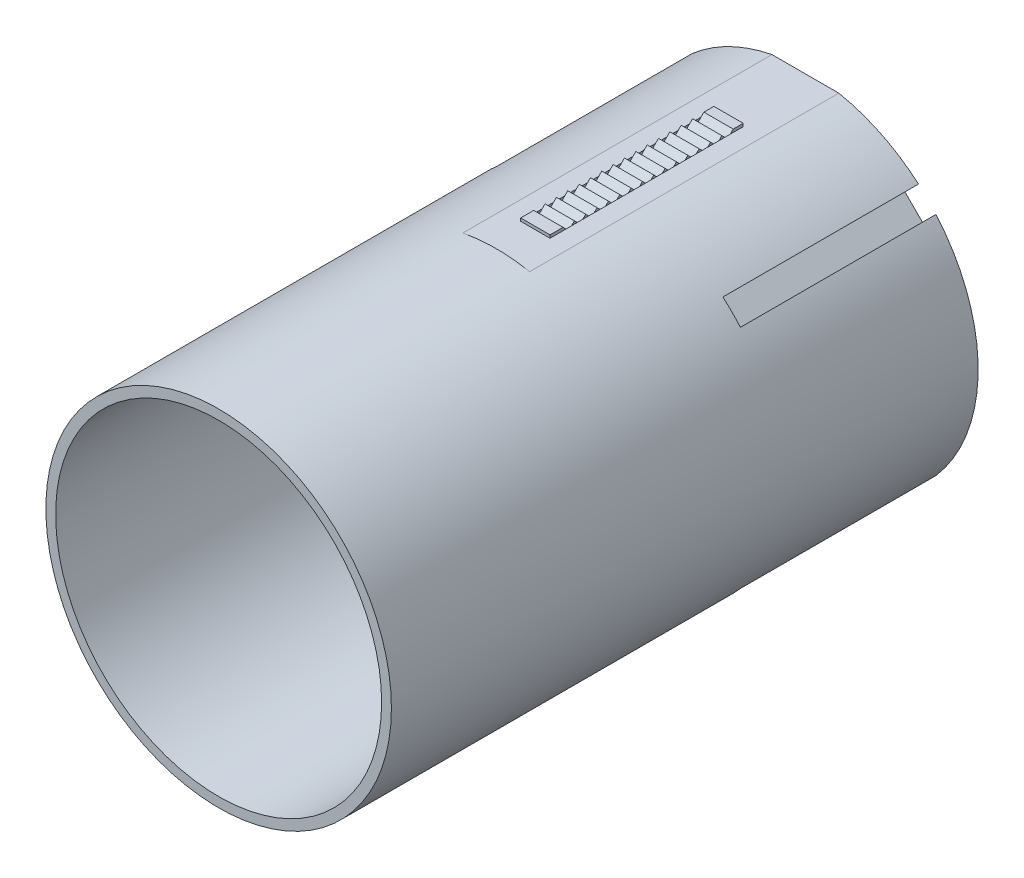
SolidWorks part; units mm, degrees
ref_plane "Ebene vorne" through (0, 0, 0) normal (0, 0, 1) x (1, 0, 0)
ref_plane "Ebene oben" through (0, 0, 0) normal (0, 1, 0) x (1, 0, 0)
ref_plane "Ebene rechts" through (0, 0, 0) normal (1, 0, 0) x (0, 0, -1)
sketch "Skizze1" plane through (0, 0, 0) normal (0, 0, 1) x (1, 0, 0)
  circle A0 centre (0, 0) radius 25
  circle A1 centre (0, 0) radius 26.5
  dimension "D1" = 50
  dimension "D2" = 1.5
extrude "Aufsatz-Linear austragen1" add sketch "Skizze1" along normal blind 90
sketch "Skizze2" plane through (0, 0, 0) normal (1, 0, 0) x (0, 0, -1)
  line L0 (0, 26.5) -> (0, 26)
  line L1 (0, -26.5) -> (0, 26.5) construction
  line L2 (0, 26) -> (-47.4208, 26)
  line L3 (-47.4208, 26) -> (-47.4208, 26.5)
  line L4 (0, 26.5) -> (-90, 26.5) construction
  line L5 (-47.4208, 26.5) -> (0, 26.5)
  dimension "D1" = 0.5
extrude "Schnitt-Linear austragen1" cut sketch "Skizze2" against normal through all and the other way through all
sketch "Skizze4" plane through (0, 0, 0) normal (0, 0, -1) x (-1, 0, 0)
  line L0 (0, 26) -> (0, 19.8792) construction
  line L1 (5.1235, 26) -> (-5.1235, 26) construction
  line L2 (8.5294, 23.5) -> (-8.5294, 23.5)
  line L4 (-8.5294, 23.5) -> (-5.3603, 25.2043)
  line L5 (-5.3603, 25.2043) -> (5.3603, 25.2043)
  line L6 (8.5294, 23.5) -> (5.3603, 25.2043)
  circle A0 centre (0, 0) radius 25 construction
  point P12 (0, 25.2043)
  point P13 (0, 23.5)
  dimension "D1" = 2.5
extrude "Aufsatz-Linear austragen2" add sketch "Skizze4" against normal up to surface (47.4208 mm away) up to face at (0, 26.25, 47.4208)
sketch "Skizze5" plane through (0, 0, 0) normal (1, 0, 0) x (0, 0, -1)
  line L0 (-41.4208, 26) -> (-41.4208, 25.9992)
  line L1 (0, 26) -> (-47.4208, 26) construction
  line L2 (-41.4208, 25.9992) -> (-11.7833, 25.9992) construction
  line L3 (-11.7833, 26) -> (-11.7833, 25.9992)
  line L4 (-11.7833, 25.9992) -> (-11.7833, 26.4492)
  line L5 (-41.4208, 25.9992) -> (-41.4208, 26.4492)
  line L6 (-41.4208, 26.4492) -> (-39.4208, 26.4492)
  line L7 (-11.7833, 26) -> (-41.4208, 26)
  line L8 (-39.4208, 26.4492) -> (-38.5508, 25.5792)
  line L9 (-38.5508, 25.5792) -> (-37.6808, 26.4492)
  line L10 (-39.4208, 26.4492) -> (-39.4208, 26) construction
  line L11 (-47.4208, 26) -> (-47.4208, 26.5) construction
  line L12 (-37.6808, 26.4492) -> (-36.8108, 25.5792)
  line L13 (-36.8108, 25.5792) -> (-35.9408, 26.4492)
  line L14 (-35.9408, 26.4492) -> (-35.0708, 25.5792)
  line L15 (-35.0708, 25.5792) -> (-34.2008, 26.4492)
  line L16 (-34.2008, 26.4492) -> (-33.3308, 25.5792)
  line L17 (-33.3308, 25.5792) -> (-32.4608, 26.4492)
  line L18 (-32.4608, 26.4492) -> (-31.5908, 25.5792)
  line L19 (-31.5908, 25.5792) -> (-30.7208, 26.4492)
  line L20 (-30.7208, 26.4492) -> (-29.8508, 25.5792)
  line L21 (-29.8508, 25.5792) -> (-28.9808, 26.4492)
  line L22 (-28.9808, 26.4492) -> (-28.1108, 25.5792)
  line L23 (-28.1108, 25.5792) -> (-27.2408, 26.4492)
  line L24 (-27.2408, 26.4492) -> (-26.3708, 25.5792)
  line L25 (-26.3708, 25.5792) -> (-25.5008, 26.4492)
  line L26 (-25.5008, 26.4492) -> (-24.6308, 25.5792)
  line L27 (-24.6308, 25.5792) -> (-23.7608, 26.4492)
  line L28 (-23.7608, 26.4492) -> (-22.8908, 25.5792)
  line L29 (-22.8908, 25.5792) -> (-22.0208, 26.4492)
  line L30 (-22.0208, 26.4492) -> (-21.1508, 25.5792)
  line L31 (-21.1508, 25.5792) -> (-20.2808, 26.4492)
  line L32 (-11.7833, 26.4492) -> (-13.3208, 26.4492)
  line L33 (-20.2808, 26.4492) -> (-19.4108, 25.5792)
  line L34 (-19.4108, 25.5792) -> (-18.5408, 26.4492)
  line L35 (-18.5408, 26.4492) -> (-17.6708, 25.5792)
  line L36 (-17.6708, 25.5792) -> (-16.8008, 26.4492)
  line L37 (-16.8008, 26.4492) -> (-15.9308, 25.5792)
  line L38 (-15.9308, 25.5792) -> (-15.0608, 26.4492)
  line L39 (-15.0608, 26.4492) -> (-14.1908, 25.5792)
  line L40 (-14.1908, 25.5792) -> (-13.3208, 26.4492)
  line L91 (29.3092, 25.5792) -> (30.1792, 26.4492) [skipped]
  line L92 (28.4392, 26.4492) -> (29.3092, 25.5792) [skipped]
  line L93 (27.5692, 25.5792) -> (28.4392, 26.4492) [skipped]
  line L94 (26.6992, 26.4492) -> (27.5692, 25.5792) [skipped]
  line L95 (25.8292, 25.5792) -> (26.6992, 26.4492) [skipped]
  line L96 (24.9592, 26.4492) -> (25.8292, 25.5792) [skipped]
  line L97 (24.0892, 25.5792) -> (24.9592, 26.4492) [skipped]
  line L98 (23.2192, 26.4492) -> (24.0892, 25.5792) [skipped]
  line L99 (22.3492, 25.5792) -> (23.2192, 26.4492) [skipped]
  line L100 (21.4792, 26.4492) -> (22.3492, 25.5792) [skipped]
  line L101 (20.6092, 25.5792) -> (21.4792, 26.4492) [skipped]
  line L102 (19.7392, 26.4492) -> (20.6092, 25.5792) [skipped]
  line L103 (18.8692, 25.5792) -> (19.7392, 26.4492) [skipped]
  line L104 (17.9992, 26.4492) -> (18.8692, 25.5792) [skipped]
  line L105 (17.1292, 25.5792) -> (17.9992, 26.4492) [skipped]
  line L106 (16.2592, 26.4492) -> (17.1292, 25.5792) [skipped]
  line L107 (15.3892, 25.5792) -> (16.2592, 26.4492) [skipped]
  line L108 (14.5192, 26.4492) -> (15.3892, 25.5792) [skipped]
  line L109 (13.6492, 25.5792) -> (14.5192, 26.4492) [skipped]
  line L110 (12.7792, 26.4492) -> (13.6492, 25.5792) [skipped]
  line L111 (11.9092, 25.5792) -> (12.7792, 26.4492) [skipped]
  line L112 (11.0392, 26.4492) -> (11.9092, 25.5792) [skipped]
  line L113 (10.1692, 25.5792) -> (11.0392, 26.4492) [skipped]
  line L114 (9.2992, 26.4492) -> (10.1692, 25.5792) [skipped]
  line L115 (8.4292, 25.5792) -> (9.2992, 26.4492) [skipped]
  line L116 (7.5592, 26.4492) -> (8.4292, 25.5792) [skipped]
  line L117 (6.6892, 25.5792) -> (7.5592, 26.4492) [skipped]
  line L118 (5.8192, 26.4492) -> (6.6892, 25.5792) [skipped]
  line L119 (4.9492, 25.5792) -> (5.8192, 26.4492) [skipped]
  line L120 (4.0792, 26.4492) -> (4.9492, 25.5792) [skipped]
  line L121 (3.2092, 25.5792) -> (4.0792, 26.4492) [skipped]
  line L122 (2.3392, 26.4492) -> (3.2092, 25.5792) [skipped]
  line L123 (1.4692, 25.5792) -> (2.3392, 26.4492) [skipped]
  line L124 (0.5992, 26.4492) -> (1.4692, 25.5792) [skipped]
  line L125 (-0.2708, 25.5792) -> (0.5992, 26.4492) [skipped]
  line L126 (-1.1408, 26.4492) -> (-0.2708, 25.5792) [skipped]
  line L127 (-2.0108, 25.5792) -> (-1.1408, 26.4492) [skipped]
  line L128 (-2.8808, 26.4492) -> (-2.0108, 25.5792) [skipped]
  line L129 (-3.7508, 25.5792) -> (-2.8808, 26.4492) [skipped]
  line L130 (-4.6208, 26.4492) -> (-3.7508, 25.5792) [skipped]
  line L131 (-5.4908, 25.5792) -> (-4.6208, 26.4492) [skipped]
  line L132 (-6.3608, 26.4492) -> (-5.4908, 25.5792) [skipped]
  line L133 (-7.2308, 25.5792) -> (-6.3608, 26.4492) [skipped]
  line L134 (-8.1008, 26.4492) -> (-7.2308, 25.5792) [skipped]
  line L135 (-8.9708, 25.5792) -> (-8.1008, 26.4492) [skipped]
  line L136 (-9.8408, 26.4492) -> (-8.9708, 25.5792) [skipped]
  line L137 (-10.7108, 25.5792) -> (-9.8408, 26.4492) [skipped]
  line L138 (-11.6061, 26.4746) -> (-11.3775, 26.2459) [skipped]
  line L139 (-17.6454, 25.6046) -> (-17.2254, 26.0246) [skipped]
  line L140 (-12.0554, 25.9746) -> (-12.0054, 26.0246) [skipped]
  line L141 (-20.2808, 26.4492) -> (-19.4108, 25.5792) [skipped]
  line L142 (-19.3854, 25.6046) -> (-18.9654, 26.0246) [skipped]
  line L143 (-18.1161, 26.0246) -> (-17.6961, 25.6046) [skipped]
  line L144 (-16.8261, 26.4746) -> (-16.3261, 25.9746) [skipped]
  line L145 (-15.5354, 25.9746) -> (-15.0354, 26.4746) [skipped]
  line L146 (-15.0861, 26.4746) -> (-14.5861, 25.9746) [skipped]
  line L147 (-13.7954, 25.9746) -> (-13.7454, 26.0246) [skipped]
  line L148 (-12.8961, 26.0246) -> (-12.8461, 25.9746) [skipped]
  dimension "D1" = 5
  dimension "D2" = 0.45
  dimension "D3" = 45
  dimension "D4" = 1.74
  dimension "D5" = 2
  dimension "D6" = 6
  dimension "D7" = 40
extrude "Aufsatz-Linear austragen3" add sketch "Skizze5" along normal blind 2.25 and the other way blind 2.25 contours L12 L9 L7 | L14 L13 L7 | L16 L15 L7 | L18 L17 L7 | L20 L19 L7 | L22 L21 L7 | L24 L23 L7 | L26 L25 L7 | L28 L27 L7 | L30 L29 L7 | L4 L32 L31 L7 | L8 L6 L5 L7 | L33 L31 L7 | L35 L34 L7 | L37 L36 L7 | L39 L38 L7 | L6 L8 L9 L12 L13 L14 L15 L16 L17 L18 L19 L20 L21 L22 L23 L24 L25 L26 L27 L28 L29 L30 L31 L32 L4 L3 L7 L0 L5 region at (0, 26.2151, 12.6691) region at (0, 26.2171, 40.3047) region at (0, 26.1497, 37.6808) region at (0, 26.1497, 35.9408) region at (0, 26.1497, 34.2008) region at (0, 26.1497, 32.4608) region at (0, 26.1497, 30.7208) region at (0, 26.1497, 28.9808) region at (0, 26.1497, 27.2408) region at (0, 26.1497, 25.5008) region at (0, 26.1497, 23.7608) region at (0, 26.1497, 22.0208) region at (0, 26.1497, 20.2808) region at (0, 26.1497, 18.5408) region at (0, 26.1497, 16.8008) region at (0, 26.1497, 15.0608)
sketch "Skizze6" plane through (0, 0, 0) normal (0, 0, -1) x (-1, 0, 0)
  line L0 (0, 0) -> (0, 33.2301) construction
  line L1 (0, 0) -> (-25.6455, 25.6455) construction
  line L2 (-18.7383, 18.7383) -> (-16.5976, 20.8791) construction
  line L3 (-17.3948, 20.0818) -> (-15.2735, 17.9605)
  line L4 (-15.2735, 17.9605) -> (-17.9605, 15.2735)
  line L5 (-17.3948, 20.0818) -> (-18.8549, 18.8549)
  line L6 (-20.0818, 17.3948) -> (-18.8549, 18.8549)
  line L7 (-20.0818, 17.3948) -> (-17.9605, 15.2735)
  line L8 (-15.1093, 19.9176) -> (-13.1522, 17.9605)
  line L9 (-13.1522, 17.9605) -> (-17.9605, 13.1522)
  line L10 (-19.9176, 15.1093) -> (-17.9605, 13.1522)
  line L11 (-19.9176, 15.1093) -> (-19.4038, 16.7168)
  line L12 (-15.1093, 19.9176) -> (-16.7168, 19.4038)
  arc A0 (-5.1235, 26) -> (5.1235, 26) centre (0, 0) ccw construction
  arc A1 (-8.5294, 23.5) -> (8.5294, 23.5) centre (0, 0) ccw construction
  point P15 (-16.617, 16.617)
  point P22 (-15.5563, 15.5563)
  arc M11 (8.5294, 23.5) -> (-8.5294, 23.5) centre (0, 0) cw
  arc M12 (-5.1235, 26) -> (5.1235, 26) centre (0, 0) ccw
  dimension "D1" = 45
  dimension "D2" = 3
  dimension "D3" = 1.9
  dimension "D4" = 1.5
  dimension "D5" = 1.5
extrude "Schnitt-Linear austragen2" cut sketch "Skizze6" against normal blind 30 contours L7 L3 M12 M11 | L6 L7 L3 L5 M12 | L7 L4 L3 M11 region at (18.7657, 18.7657, 0) region at (18.1914, 18.1914, 0) region at (17.1389, 17.1389, 0)
extrude "Aufsatz-Linear austragen4" add sketch "Skizze6<3>" against normal blind 30 contours L10 L9 L8 L3 L4 L7 M11 region at (16.3746, 16.3746, 0)
sketch "Skizze6<3>" plane through (0, 0, 0) normal (0, 0, -1) x (-1, 0, 0) same geometry as "Skizze6"
sketch "Skizze7" plane through (0, 0, 30) normal (0, 0, 1) x (1, 0, 0)
  line L0 (13.1522, 17.9605) -> (17.9605, 13.1522)
  line L1 (17.9605, 13.1522) -> (19.9176, 15.1093)
  line L2 (19.9176, 15.1093) -> (18.2547, 18.0002)
  line L3 (18.2547, 18.0002) -> (15.3523, 20.1606)
  line L4 (15.3523, 20.1606) -> (13.1522, 17.9605)
  arc A0 (19.9176, 15.1093) -> (18.97, 16.283) centre (0, 0) ccw construction
extrude "Aufsatz-Linear austragen5" add sketch "Skizze7" along normal blind 1
mirror "Spiegeln1" about plane through (0, 0, 0) normal (1, 0, 0) of "Aufsatz-Linear austragen5", "Schnitt-Linear austragen2", "Aufsatz-Linear austragen4"
mirror "Spiegeln2" about plane through (0, 0, 0) normal (0, 1, 0) of "Spiegeln1"
extrude "Schnitt-Linear austragen3" cut sketch "Skizze5<3>" against normal blind 2.25 and the other way blind 2.25 contours L8 L9 L7 | L12 L13 L7 | L14 L15 L7 | L16 L17 L7 | L18 L19 L7 | L20 L21 L7 | L22 L23 L7 | L24 L25 L7 | L26 L27 L7 | L28 L29 L7 | L30 L31 L7 | L33 L34 L7 | L35 L36 L7 | L37 L38 L7 | L39 L40 L7 region at (0, 25.8597, 38.5508) region at (0, 25.8597, 36.8108) region at (0, 25.8597, 35.0708) region at (0, 25.8597, 33.3308) region at (0, 25.8597, 31.5908) region at (0, 25.8597, 29.8508) region at (0, 25.8597, 28.1108) region at (0, 25.8597, 26.3708) region at (0, 25.8597, 24.6308) region at (0, 25.8597, 22.8908) region at (0, 25.8597, 21.1508) region at (0, 25.8597, 19.4108) region at (0, 25.8597, 17.6708) region at (0, 25.8597, 15.9308) region at (0, 25.8597, 14.1908)
sketch "Skizze5<3>" plane through (0, 0, 0) normal (1, 0, 0) x (0, 0, -1) same geometry as "Skizze5"
sketch "Skizze8" plane through (0, 0, 0) normal (1, 0, 0) x (0, 0, -1)
  line L0 (-30.9779, 29.3049) -> (-30.9779, -33.0205)
  line L1 (-30.9779, -33.0205) -> (-101.2654, -31.5166)
  line L2 (-101.2654, -31.5166) -> (-96.09, 35.8072)
  line L3 (-96.09, 35.8072) -> (-30.9779, 29.3049)
extrude "Schnitt-Linear austragen4" [suppressed] cut sketch "Skizze8" against normal through all and the other way through all
